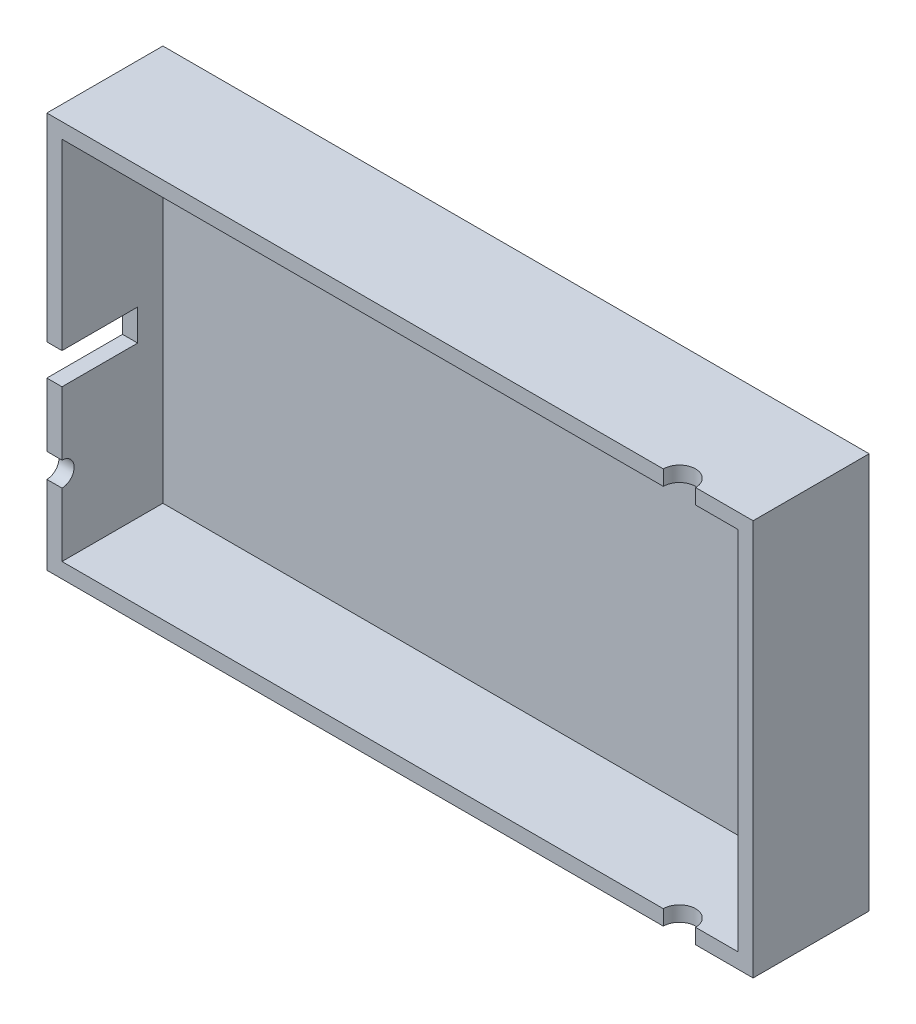
SolidWorks part; units mm, degrees
ref_plane "前视基准面" through (0, 0, 0) normal (0, 0, 1) x (1, 0, 0)
ref_plane "上视基准面" through (0, 0, 0) normal (0, 1, 0) x (1, 0, 0)
ref_plane "右视基准面" through (0, 0, 0) normal (1, 0, 0) x (0, 0, -1)
sketch "草图1" plane through (0, 0, 0) normal (0, 0, 1) x (1, 0, 0)
  line L0 (30, -26) -> (-30, -26) construction
  line L1 (-40, 13.25) -> (30, 13.25)
  line L2 (-40, 13.25) -> (-40, -26)
  line L3 (-40, -26) -> (30, -26)
  line L4 (30, 13.25) -> (30, -26)
  line L5 (-40, 13.25) -> (30, -26) construction
  line L6 (-40, -26) -> (30, 13.25) construction
  line L7 (-30, 13.25) -> (30, 13.25) construction
  line L8 (30, 13.25) -> (30, -26) construction
  point P0 (-8.4392, -4.4466)
  dimension "D2" = 70
extrude "凸台-拉伸1" add sketch "草图1" along normal blind 11.5
shell "抽壳1" thickness 1.5 removed face at (-5, -6.375, 11.5)
sketch "草图4" plane through (0, -26, 0) normal (0, -1, 0) x (1, 0, 0)
  circle A0 centre (22.7, 11.5) radius 1.6
  circle A1 centre (22.7, 11.5) radius 1.5 construction
  dimension "D1" = 0.1
extrude "3MM孔切除-拉伸2" cut sketch "草图4" against normal through all
sketch "草图6" plane through (0, 13.25, 0) normal (0, 1, 0) x (1, 0, 0)
  circle A0 centre (10.5, -11.5) radius 1.1
  circle A1 centre (10.5, -11.5) radius 1 construction
  dimension "D1" = 0.1
sketch "草图10" plane through (-40, 0, 0) normal (-1, 0, 0) x (0, 0, 1)
  circle A0 centre (11.5, -17) radius 1 construction
  circle A1 centre (11.5, -17) radius 1 construction
  circle A2 centre (11.5, -17) radius 1.2
  dimension "D1" = 0.2
extrude "切除-拉伸3" cut sketch "草图10" against normal blind 40
sketch "草图11" plane through (-40, 0, 0) normal (-1, 0, 0) x (0, 0, 1)
  line L0 (11.5, 13.25) -> (11.5, -15.8) construction
  line L1 (11.5, -6.4) -> (4, -6.4)
  line L2 (11.5, -6.4) -> (11.5, -9.5)
  line L3 (11.5, -9.5) -> (4, -9.5)
  line L4 (4, -6.4) -> (4, -9.5)
  line L6 (11.5, -9.5) -> (19, -9.5) construction
  line L7 (19, -6.4) -> (11.5, -6.4) construction
  dimension "D1" = 7.5
extrude "切除-拉伸4" cut sketch "草图11" against normal up to next
